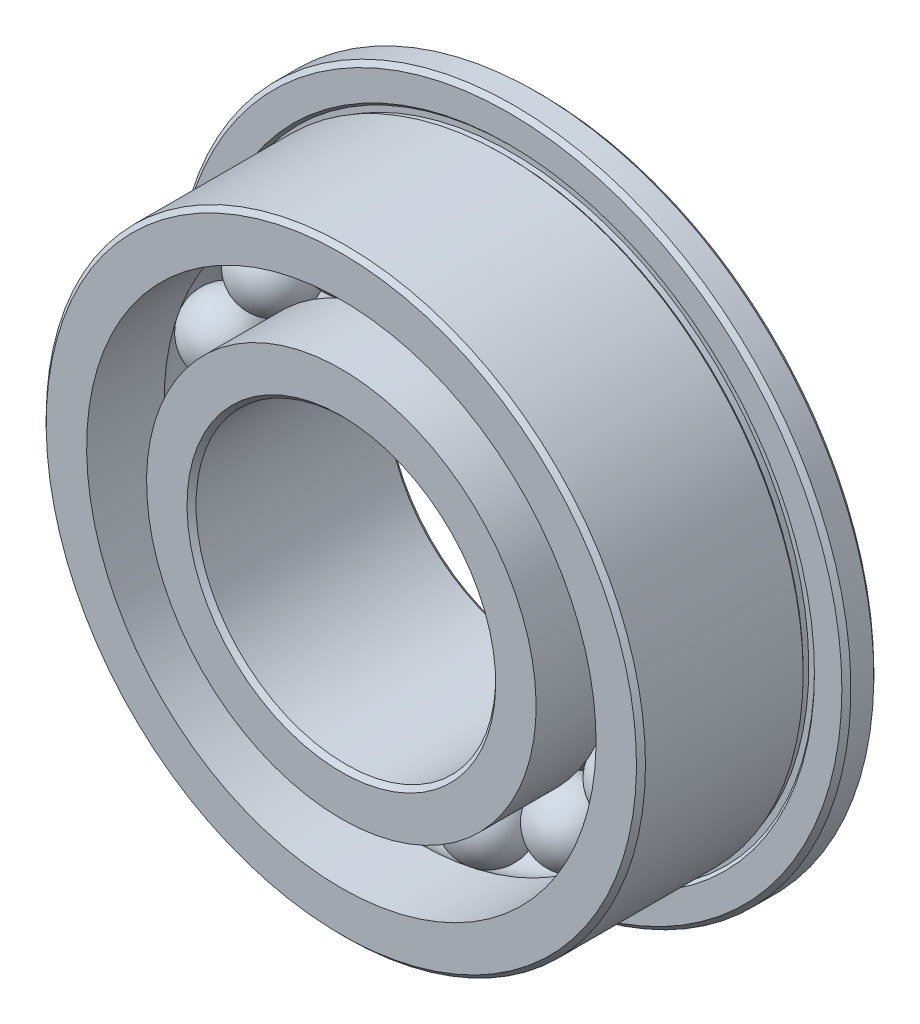
SolidWorks part; units mm, degrees
ref_plane "Front Plane" through (0, 0, 0) normal (0, 0, 1) x (1, 0, 0)
ref_plane "Top Plane" through (0, 0, 0) normal (0, 1, 0) x (1, 0, 0)
ref_plane "Right Plane" through (0, 0, 0) normal (1, 0, 0) x (0, 0, -1)
sketch "Sketch1" plane through (0, 0, 0) normal (1, 0, 0) x (0, 0, -1)
  line L0 (0, 4.7625) -> (0, -4.7625) construction
  line L1 (-1.5875, 4.7625) -> (1.5875, 4.7625) construction
  line L2 (0, 0) -> (1.5875, 0) construction
  line L3 (1.5875, 5.3594) -> (1.5875, -5.3594) construction
  line L4 (1.5875, -5.3594) -> (1.0795, -5.3594) construction
  line L5 (1.5875, 2.3813) -> (0, 2.3813) construction
  line L6 (1.5875, 2.3813) -> (1.5875, -2.3813) construction
  dimension "OD" = 9.525
  dimension "Width" = 3.175
  dimension "Flange Dia." = 10.7188
  dimension "Flange Thickness" = 0.508
  dimension "ID" = 4.7625
sketch "Sketch2" plane through (0, 0, 0) normal (1, 0, 0) x (0, 0, -1)
  line L0 (1.5875, 5.3594) -> (1.0795, 5.3594)
  line L1 (1.0795, 5.3594) -> (1.0795, 4.8523)
  line L2 (0.9897, 4.7625) -> (-1.5875, 4.7625)
  line L3 (-1.5875, 4.7625) -> (-1.5875, 4.0481)
  line L4 (-1.5875, 4.0481) -> (-0.3572, 4.0481)
  line L5 (1.5875, 5.3594) -> (1.5875, -5.3594) construction
  line L6 (1.5875, 4.0481) -> (1.5875, 5.3594)
  line L7 (1.5875, 2.3813) -> (-1.5875, 2.3813)
  line L8 (-1.5875, 2.3813) -> (-1.5875, 3.0956)
  line L9 (-1.5875, 3.0956) -> (-0.3572, 3.0956)
  line L10 (1.5875, 3.0956) -> (1.5875, 2.3813)
  line L11 (0, 4.7625) -> (0, 2.3813) construction
  line L12 (-0.5953, 3.5719) -> (0.5953, 3.5719) construction
  line L13 (0.3572, 4.0481) -> (1.5875, 4.0481)
  line L14 (0.3572, 3.0956) -> (1.5875, 3.0956)
  line L15 (1.0795, 4.8523) -> (1.1244, 4.8074)
  line L16 (1.1244, 4.8074) -> (1.1244, 4.7176)
  line L17 (1.1244, 4.7176) -> (1.0346, 4.7176)
  line L18 (1.0346, 4.7176) -> (0.9897, 4.7625)
  line L19 (1.0795, 4.7625) -> (1.1244, 4.7176) construction
  line L20 (1.1244, 4.8074) -> (1.0346, 4.7176) construction
  line L21 (0.9897, 4.7625) -> (1.0795, 4.7625) construction
  line L22 (1.0795, 4.7625) -> (1.0795, 4.8523) construction
  circle A0 centre (0, 3.5719) radius 0.5953 construction
  arc A1 (-0.3572, 4.0481) -> (0.3572, 4.0481) centre (0, 3.5719) cw
  arc A2 (-0.3572, 3.0956) -> (0.3572, 3.0956) centre (0, 3.5719) ccw
  dimension "D1" = 2.3812
  dimension "Ball Dia." = 1.1906
  dimension "D2" = 135
  dimension "D3" = 0.127
  dimension "D4" = 0.9525
  dimension "Race Thickness" = 0.7144
revolve "Revolve1" add sketch "Sketch2" angle 360 about L2
fillet "Fillet1" radius 0.0714 3 edges at (0, -5.3594, -1.5875) (0, -5.3594, -1.0795) (0, -4.7625, 1.5875) profile chamfer
sketch "Sketch3" plane through (0, 0, 0) normal (0, 0, 1) x (1, 0, 0)
  line L0 (-2.3813, 0) -> (2.3813, 0) construction
  line L1 (-4.7625, 0) -> (4.7625, 0) construction
  point P5 (0, 0)
  dimension "ID2" = 4.7625
  dimension "OD2" = 9.525
fillet "Fillet2" radius 0.0714 2 edges at (0, -2.3813, -1.5875) (0, -2.3813, 1.5875) profile chamfer
sketch "Sketch7" plane through (0, 0, 0) normal (0, 0, 1) x (1, 0, 0)
  line L0 (0, 4.1672) -> (0, 2.9766)
  line L1 (0, 5.3594) -> (0, -5.3594) construction
  line L2 (-0.7044, 4.1672) -> (0, 0) construction
  line L3 (0, 0) -> (0.7044, 4.1672) construction
  line L4 (0.7044, 4.1672) -> (-0.7044, 4.1672) construction
  circle A0 centre (0, 3.5719) radius 0.5953 construction
  circle A1 centre (0, 0) radius 4.1672 construction
  circle A2 centre (0, 0) radius 2.9766 construction
  arc A4 (0, 4.1672) -> (0, 2.9766) centre (0, 3.5719) ccw
  dimension "D1" = 19.188
revolve "Revolve3" add sketch "Sketch7" angle 360 about L0
pattern_circular "CirPattern3" count 15 over 360 about axis through (0, 0, 0) along (0, 0, -1) of bodies 107
sketch "Sketch8" [suppressed] plane through (0, 0, 0) normal (1, 0, 0) x (0, 0, -1)
  line L1 (-1.1906, 2.0241) -> (-1.0477, 2.0241)
  line L2 (-1.1906, 2.0241) -> (-1.1906, 2.1431)
  line L3 (-1.1906, 2.1431) -> (-1.0477, 2.1431)
  line L4 (-1.0477, 2.0241) -> (-1.0477, 2.1431)
  line L5 (1.1906, 2.0241) -> (1.0478, 2.0241)
  line L6 (1.1906, 2.0241) -> (1.1906, 2.1431)
  line L7 (1.1906, 2.1431) -> (1.0478, 2.1431)
  line L8 (1.0478, 2.0241) -> (1.0478, 2.1431)
  line L9 (1.1906, 1.5478) -> (1.0478, 1.5478)
  line L10 (1.1906, 1.5478) -> (1.1906, 1.4287)
  line L11 (1.1906, 1.4287) -> (1.0478, 1.4287)
  line L12 (1.0478, 1.5478) -> (1.0478, 1.4287)
  line L13 (-1.1906, 1.5478) -> (-1.0477, 1.5478)
  line L14 (-1.1906, 1.5478) -> (-1.1906, 1.4287)
  line L15 (-1.1906, 1.4287) -> (-1.0477, 1.4287)
  line L16 (-1.0477, 1.5478) -> (-1.0477, 1.4287)
  dimension "D1" = 0.2381
  dimension "D2" = 0.2858
revolve "Cut-Revolve1" [suppressed] cut sketch "Sketch8" angle 360 about L2
sketch "Sketch9" [suppressed] plane through (0, 0, 0) normal (1, 0, 0) x (0, 0, -1)
  line L0 (-1.0477, 2.1431) -> (-1.0477, 1.8657)
  line L1 (-1.0477, 1.8657) -> (-1.1192, 1.7419)
  line L2 (-1.1192, 1.7419) -> (-1.1192, 1.4645)
  line L3 (1.1192, 1.4645) -> (1.1192, 1.4287) construction
  line L4 (1.0478, 2.1431) -> (1.0478, 1.8657)
  line L5 (1.0478, 1.8657) -> (1.1192, 1.7419)
  line L6 (1.1192, 1.7419) -> (1.1192, 1.4645)
  line L7 (1.1906, 1.4287) -> (1.0478, 1.4287) construction
  line L8 (-1.0835, 2.1431) -> (-1.0835, 1.8752)
  line L9 (-1.0835, 1.8752) -> (-1.1549, 1.7515)
  line L10 (-1.1549, 1.7515) -> (-1.1549, 1.4645)
  line L11 (-1.0477, 2.1431) -> (-1.0835, 2.1431)
  line L12 (-1.1192, 1.4645) -> (-1.1549, 1.4645)
  line L13 (1.0835, 2.1431) -> (1.0835, 1.8752)
  line L14 (1.0835, 1.8752) -> (1.1549, 1.7515)
  line L15 (1.1549, 1.7515) -> (1.1549, 1.4645)
  line L16 (1.0478, 2.1431) -> (1.0835, 2.1431)
  line L17 (1.1192, 1.4645) -> (1.1549, 1.4645)
  line L18 (-1.0477, 1.8657) -> (-1.0477, 2.6) construction
  line L19 (1.0478, 1.8657) -> (1.0478, 2.1431) construction
  line L20 (-1.0477, 1.4287) -> (-1.1906, 1.4287) construction
  line L22 (-1.1192, 1.4645) -> (-1.1192, 1.4287) construction
  dimension "D2" = 150
  dimension "D1" = 150
  dimension "D5" = 0.1429
  dimension "D3" = 0.0357
  dimension "D4" = 0.0357
revolve "Revolve4" [suppressed] add sketch "Sketch9" angle 360 about L2
ref_axis "Center Axis 1" through (0, 0, -0.8731) along (0, 0, 1)
ref_plane "Contact Plane 1" through (0, 0, -1.0795) normal (0, 0, 1) x (1, 0, 0)
equation "\"Ball Dia.@Sketch2\"=\"D1@Sketch2\"*.5"
equation "\"D3@Sketch2\"=\"Flange Thickness@Sketch1\"/4"
equation "\"D1@Fillet1\"=\"Race Thickness@Sketch2\"/10"
equation "\"ID2@Sketch3\" = \"ID@Sketch1\""
equation "\"OD2@Sketch3\" = \"OD@Sketch1\""
equation "\"D1@Fillet2\"=\"Race Thickness@Sketch2\"/10"
equation "\"D1@CirPattern3\"=360/\"D1@Sketch7\"-4"
equation "\"D1@Sketch8\"=\"Race Thickness@Sketch2\"/3"
equation "\"D2@Sketch8\"=\"Race Thickness@Sketch2\"/2.5"
equation "\"D3@Sketch9\"=\"D5@Sketch9\"/4"
equation "\"D4@Sketch9\"=\"D5@Sketch9\"/4"
equation "\"D1@Sketch9\"=\"D2@Sketch9\""
equation "\"D4@Sketch2\"=\"D1@Sketch2\"*.4"
